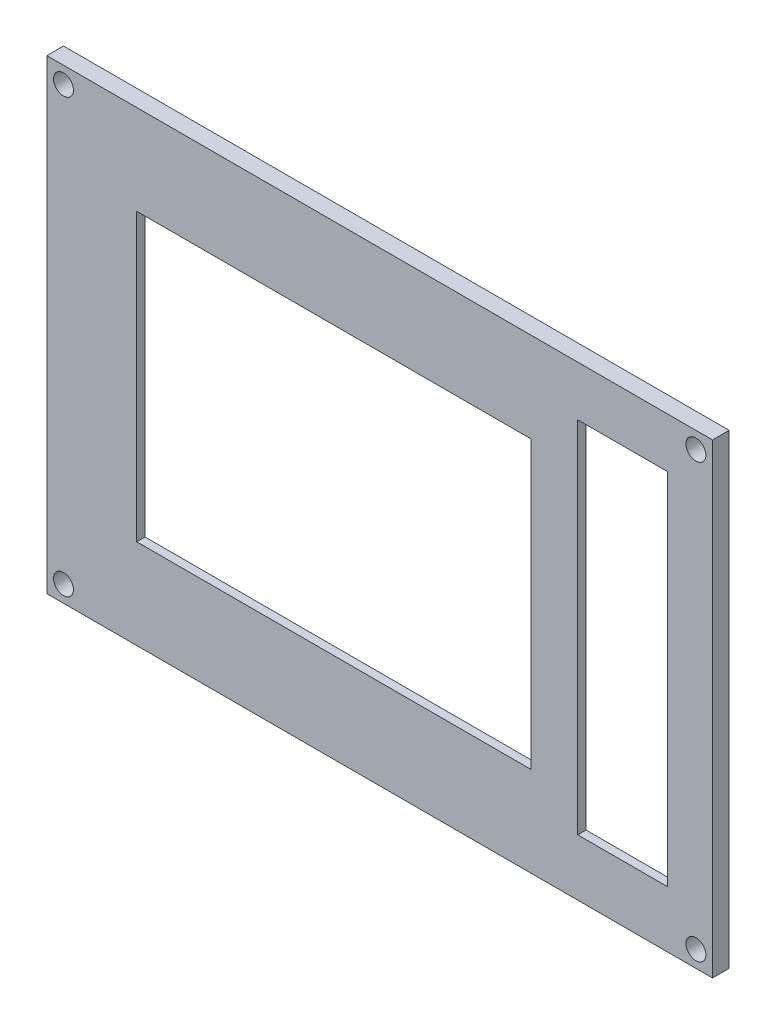
SolidWorks part; units mm, degrees
ref_plane "Front Plane" through (0, 0, 0) normal (0, 0, 1) x (1, 0, 0)
ref_plane "Top Plane" through (0, 0, 0) normal (0, 1, 0) x (1, 0, 0)
ref_plane "Right Plane" through (0, 0, 0) normal (1, 0, 0) x (0, 0, -1)
sketch "Sketch1" plane through (0, 0, 0) normal (0, 0, 1) x (1, 0, 0)
  line L0 (8.5, 51.5) -> (67.75, 51.5)
  line L1 (0, 0) -> (90, 0)
  line L2 (0, 0) -> (0, 60)
  line L3 (0, 60) -> (90, 60)
  line L4 (90, 0) -> (90, 60)
  line L5 (8.5, 51.5) -> (8.5, 8.5)
  line L6 (8.5, 8.5) -> (67.75, 8.5)
  line L7 (67.75, 51.5) -> (67.75, 8.5)
  line L8 (45, 60) -> (45, 65) construction
  line L9 (-5, -5) -> (95, -5)
  line L10 (-5, -5) -> (-5, 65)
  line L11 (-5, 65) -> (95, 65)
  line L12 (95, -5) -> (95, 65)
  line L13 (0, 30) -> (-5, 30) construction
  line L14 (45, 0) -> (45, -5) construction
  line L15 (90, 30) -> (95, 30) construction
  line L16 (0, 60) -> (-5, 65) construction
  line L17 (76.5, 44.5) -> (86.5, 44.5)
  line L18 (76.5, 44.5) -> (76.5, 36.5)
  line L19 (76.5, 36.5) -> (86.5, 36.5)
  line L20 (86.5, 44.5) -> (86.5, 36.5)
  line L21 (76.5, 34.5) -> (86.5, 34.5)
  line L22 (76.5, 34.5) -> (76.5, 26.5)
  line L23 (76.5, 26.5) -> (86.5, 26.5)
  line L24 (86.5, 34.5) -> (86.5, 26.5)
  line L25 (76.5, 24.5) -> (86.5, 24.5)
  line L26 (76.5, 24.5) -> (76.5, 16.5)
  line L27 (76.5, 16.5) -> (86.5, 16.5)
  line L28 (86.5, 24.5) -> (86.5, 16.5)
  line L29 (76.5, 14.5) -> (86.5, 14.5)
  line L30 (76.5, 14.5) -> (76.5, 6.5)
  line L31 (76.5, 6.5) -> (86.5, 6.5)
  line L32 (86.5, 14.5) -> (86.5, 6.5)
  line L33 (76.5, 46.5) -> (86.5, 46.5)
  line L34 (76.5, 46.5) -> (76.5, 54.5)
  line L35 (76.5, 54.5) -> (86.5, 54.5)
  line L36 (86.5, 46.5) -> (86.5, 54.5)
  line L37 (95, 65) -> (90, 60) construction
  line L38 (95, -5) -> (90, 0) construction
  line L39 (0, 0) -> (-5, -5) construction
  line L40 (76.5, 6.5) -> (74.75, 6.5) construction
  line L41 (88.25, 57.5) -> (74.75, 57.5)
  line L42 (88.25, 57.5) -> (88.25, 3.5)
  line L43 (88.25, 3.5) -> (74.75, 3.5)
  line L44 (74.75, 57.5) -> (74.75, 3.5)
  line L45 (76.5, 6.5) -> (76.5, 3.5) construction
  line L46 (86.5, 6.5) -> (86.5, 3.5) construction
  line L47 (86.5, 6.5) -> (88.25, 6.5) construction
  line L48 (86.5, 54.5) -> (88.25, 54.5) construction
  line L49 (86.5, 54.5) -> (86.5, 57.5) construction
  line L50 (76.5, 54.5) -> (74.75, 54.5)
  line L51 (76.5, 54.5) -> (76.5, 57.5) construction
  circle A0 centre (-2.5, -2.5) radius 1.5
  circle A1 centre (-2.5, 62.5) radius 1.5
  circle A2 centre (92.5, 62.5) radius 1.5
  circle A3 centre (92.5, -2.5) radius 1.5
  dimension "D16" = 3
  dimension "D1" = 90
  dimension "D2" = 60
  dimension "D3" = 8.5
  dimension "D4" = 8.5
  dimension "D5" = 8.5
  dimension "D6" = 22.25
  dimension "D7" = 5
  dimension "D8" = 10
  dimension "D9" = 8
  dimension "D10" = 6.5
  dimension "D11" = 16.5
  dimension "D12" = 26.5
  dimension "D13" = 36.5
  dimension "D14" = 46.5
  dimension "D15" = 3.5
  dimension "D17" = 3
  dimension "D18" = 1.75
extrude "Boss-Extrude3" add sketch "Sketch1" against normal blind 1.25 contours L1 L4 L3 L2 L44 L41 L42 L43 L0 L7 L6 L5 region at (1.0817, 30, 0)
extrude "Boss-Extrude4" add sketch "Sketch1<6>" against normal blind 2.5 contours L9 L12 L11 L10 A3 A2 A1 A0 L4 L1 L2 L3 region at (-3.7793, 30, 0)
sketch "Sketch1<6>" plane through (0, 0, 0) normal (0, 0, 1) x (1, 0, 0) same geometry as "Sketch1"
